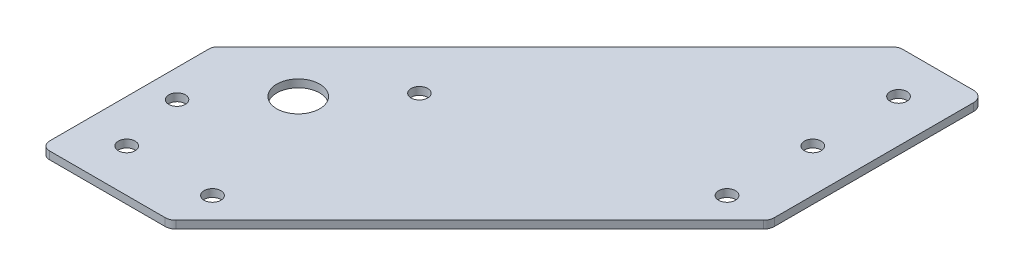
SolidWorks part; units mm, degrees
ref_plane "Front Plane" through (0, 0, 0) normal (0, 0, 1) x (1, 0, 0)
ref_plane "Top Plane" through (0, 0, 0) normal (0, 1, 0) x (1, 0, 0)
ref_plane "Right Plane" through (0, 0, 0) normal (1, 0, 0) x (0, 0, -1)
sketch "Sketch1" plane through (0, 0, 0) normal (0, 1, 0) x (1, 0, 0)
  line L0 (0, 0) -> (0, 152.4)
  line L1 (0, 152.4) -> (-25.4, 152.4)
  line L2 (-25.4, 152.4) -> (-152.4, 25.4)
  line L3 (-152.4, 25.4) -> (-152.4, 0)
  line L4 (-152.4, 0) -> (0, 0)
  circle A0 centre (-12.7, 12.7) radius 2.4892
  circle A1 centre (-38.1, 12.7) radius 2.4892
  circle A2 centre (-63.5, 12.7) radius 2.4892
  circle A3 centre (-88.9, 12.7) radius 2.4892
  circle A4 centre (-114.3, 12.7) radius 2.4892
  circle A5 centre (-12.7, 38.1) radius 2.4892
  circle A6 centre (-12.7, 63.5) radius 2.4892
  circle A7 centre (-12.7, 88.9) radius 2.4892
  circle A8 centre (-12.7, 114.3) radius 2.4892
  circle A9 centre (-139.7, 12.7) radius 2.4892
  circle A13 centre (-12.7, 139.7) radius 2.4892
  circle A17 centre (-101.6, 50.8) radius 6.35
  dimension "D4" = 12.7
  dimension "D5" = 12.7
  dimension "D8" = 12.7
  dimension "D1" = 152.4
  dimension "D2" = 25.4
  dimension "D3" = 152.4
  dimension "D9" = 101.6
  dimension "D10" = 50.8
  dimension "D11" = 25.4
  dimension "D6" = 6
  dimension "D7" = 6
extrude "Boss-Extrude2" add sketch "Sketch1" along normal mid plane 2.286
sketch "Sketch2" plane through (0, 1.143, 0) normal (0, 1, 0) x (1, 0, 0)
  line L0 (0, 0) -> (0, 88.9)
  line L1 (0, 0) -> (0, 152.4) construction
  line L2 (0, 88.9) -> (-88.9, 0)
  line L3 (-152.4, 0) -> (0, 0) construction
  line L4 (-88.9, 0) -> (0, 0)
  dimension "D1" = 45
  dimension "D2" = 88.9
  dimension "D3" = 88.9
extrude "Cut-Extrude1" cut sketch "Sketch2" against normal through all
sketch "Sketch3" plane through (0, 1.143, 0) normal (0, 1, 0) x (1, 0, 0)
  line L0 (-88.9, 0) -> (-88.9, 15.1204)
  line L1 (-88.9, 15.1204) -> (-9.2623, 94.7581)
  line L2 (-9.2623, 94.7581) -> (0, 88.9)
  line L3 (0, 88.9) -> (-88.9, 0)
extrude "Boss-Extrude3" [suppressed] add sketch "Sketch3" against normal blind 2.286
fillet "Fillet3" radius 3.175 6 edges at (-152.4, 0, 0) (-25.4, 0, -152.4) (0, 0, -152.4) (0, 0, -88.9) (-88.9, 0, 0) (-152.4, 0, -25.4)
ref_plane "Plane1" through (-152.4, 1.143, -24.0849) normal (0, 0, 1) x (1, 0, 0)
sketch "Sketch5" plane through (0, 1.143, 0) normal (0, 1, 0) x (1, 0, 0)
  line L0 (0, 0) -> (0, 152.4) construction
  line L1 (0, 152.4) -> (-152.4, 152.4) construction
  line L2 (0, 0) -> (-152.4, 0) construction
  line L3 (-152.4, 0) -> (-152.4, 152.4) construction
  dimension "D1" = 152.4
  dimension "D2" = 152.4
hole_wizard "#10 (0.1935) Diameter Hole1" positions "Sketch7" profile "Sketch6" hole size "#10" standard "ANSI Inch" end condition through all
sketch "Sketch7" plane through (0, 1.143, 0) normal (0, 1, 0) x (1, 0, 0)
  line L0 (-118.7264, 32.0425) -> (-84.4736, 69.5575) construction
  circle A0 centre (-101.6, 50.8) radius 6.35 construction
  point P0 (-118.7264, 32.0425)
  point P2 (-84.4736, 69.5575)
  point P10 (-101.6, 50.8)
  dimension "D1" = 50.8
sketch "Sketch6" plane through (-118.7264, 1.143, -32.0425) normal (1, 0, 0) x (0, 0, 1)
  line L0 (0, 0) -> (0, 2.286)
  line L1 (0, 2.286) -> (2.4574, 2.286)
  line L2 (2.4574, 2.286) -> (2.4574, 0)
  line L5 (2.4574, 0) -> (0, 0)
  line L11 (0, -6.35) -> (0, 107.95) construction
  dimension "Thru Hole Dia." = 4.9149
  dimension "Thru Hole Depth" = 2.286
sketch "Sketch8" plane through (0, 1.143, 0) normal (0, 1, 0) x (1, 0, 0)
  line L1 (-152.4, 0) -> (-127, 0)
  line L2 (-152.4, 0) -> (-152.4, 50.8)
  line L3 (-152.4, 50.8) -> (-127, 50.8)
  line L4 (-127, 0) -> (-127, 50.8)
  dimension "D1" = 25.4
  dimension "D2" = 50.8
extrude "Cut-Extrude2" cut sketch "Sketch8" against normal blind 2.54
fillet "Fillet4" radius 2.54 2 edges at (-127, 0, 0) (-127, 0, -50.8)
equation "\"0.09inin\"=0.1"
